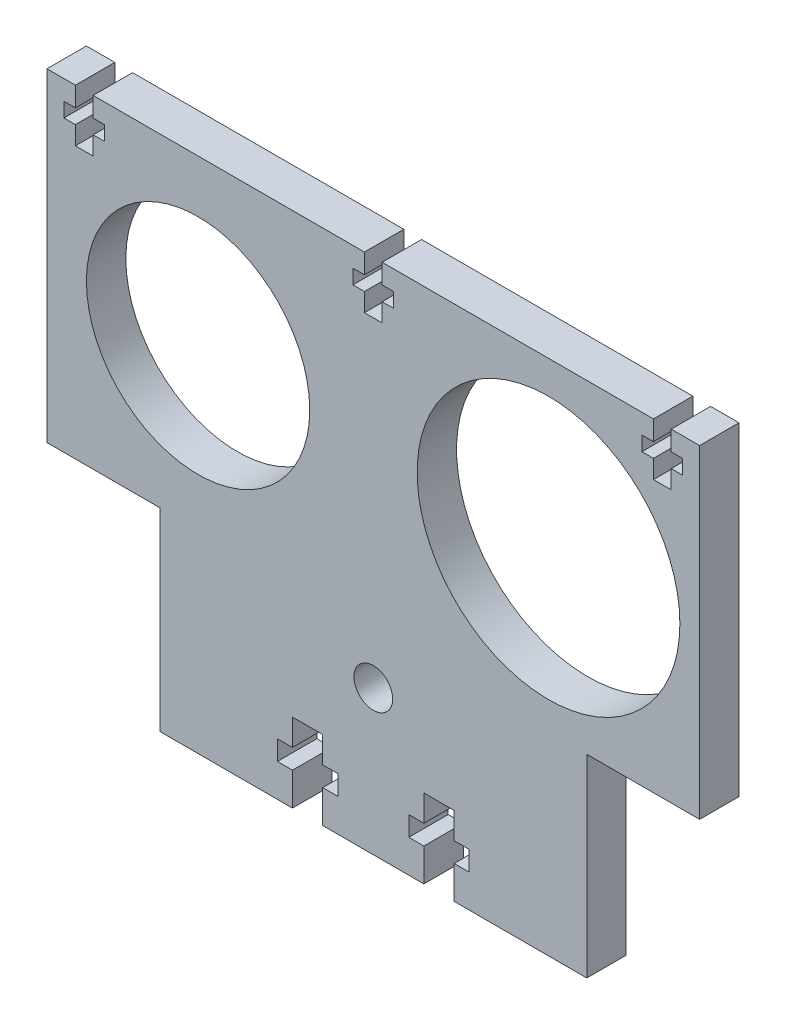
SolidWorks part; units mm, degrees
material "ABS"
ref_plane "Front Plane" through (0, 0, 0) normal (0, 0, 1) x (1, 0, 0)
ref_plane "Top Plane" through (0, 0, 0) normal (0, 1, 0) x (1, 0, 0)
ref_plane "Right Plane" through (0, 0, 0) normal (1, 0, 0) x (0, 0, -1)
sketch "Sketch1" plane through (0, 0, 0) normal (0, 0, 1) x (1, 0, 0)
  line L0 (0, 0) -> (-26.6757, 31.7908) construction
  line L1 (0, 0) -> (0, 56.7908) construction
  line L2 (-32.5, 7.5) -> (-32.5, -22)
  line L3 (-32.5, -22) -> (32.5, -22)
  line L4 (32.5, 7.5) -> (49.6757, 7.5)
  line L5 (0, 0) -> (0, -22) construction
  line L6 (49.6757, 7.5) -> (49.6757, 56.7908)
  line L7 (0, 0) -> (26.6757, 31.7908) construction
  line L10 (-32.5, 7.5) -> (-49.6757, 7.5)
  line L11 (-49.6757, 7.5) -> (-49.6757, 56.7908)
  line L12 (-49.6757, 56.7908) -> (49.6757, 56.7908)
  line L13 (32.5, 7.5) -> (32.5, -22)
  circle A0 centre (0, 0) radius 2.95
  circle A1 centre (-26.6757, 31.7908) radius 17
  circle A2 centre (26.6757, 31.7908) radius 20
  point P16 (0, 56.7908)
  dimension "D1" = 5.9
  dimension "D9" = 34
  dimension "D10" = 40
  dimension "D2" = 41.5
  dimension "D4" = 40
  dimension "D5" = 22
  dimension "D6" = 65
  dimension "D7" = 29.5
  dimension "D8" = 23
  dimension "D3" = 25
  dimension "D11" = 40
extrude "Boss-Extrude1" add sketch "Sketch1" along normal blind 6
sketch "Sketch3" plane through (0, 0, 6) normal (0, 0, 1) x (1, 0, 0)
  line L0 (-32.5, -22) -> (32.5, -22) construction
  line L1 (-12.3, -22) -> (-7.7, -22)
  line L2 (-12.3, -22) -> (-12.3, -17)
  line L3 (-12.3, -10) -> (-7.7, -10)
  line L4 (-7.7, -22) -> (-7.7, -17)
  line L5 (0, 0) -> (0, -22) construction
  line L6 (-7.7, -14) -> (-5.4, -14)
  line L7 (-14.6, -14) -> (-12.3, -14)
  line L8 (-14.6, -14) -> (-14.6, -17)
  line L9 (-14.6, -17) -> (-12.3, -17)
  line L10 (-5.4, -14) -> (-5.4, -17)
  line L11 (-12.3, -14) -> (-12.3, -10)
  line L12 (-7.7, -17) -> (-5.4, -17)
  line L13 (-7.7, -14) -> (-7.7, -10)
  line L14 (7.7, -14) -> (7.7, -10)
  line L15 (7.7, -17) -> (5.4, -17)
  line L16 (12.3, -14) -> (12.3, -10)
  line L17 (5.4, -14) -> (5.4, -17)
  line L18 (14.6, -17) -> (12.3, -17)
  line L19 (14.6, -14) -> (14.6, -17)
  line L20 (14.6, -14) -> (12.3, -14)
  line L21 (7.7, -14) -> (5.4, -14)
  line L22 (7.7, -22) -> (7.7, -17)
  line L23 (12.3, -10) -> (7.7, -10)
  line L24 (12.3, -22) -> (12.3, -17)
  line L25 (12.3, -22) -> (7.7, -22)
  point P6 (-10, -10)
  point P18 (-13.45, -17)
  dimension "D1" = 4.6
  dimension "D2" = 10
  dimension "D3" = 12
  dimension "D4" = 9.2
  dimension "D5" = 3
  dimension "D6" = 5
extrude "Cut-Extrude2" cut sketch "Sketch3" against normal through all
sketch "Sketch4" plane through (0, 0, 6) normal (0, 0, 1) x (1, 0, 0)
  line L0 (42.65, 56.7908) -> (42.65, 53.7908)
  line L1 (49.6757, 56.7908) -> (-49.6757, 56.7908) construction
  line L2 (42.65, 53.7908) -> (40.9, 53.7908)
  line L3 (40.9, 53.7908) -> (40.9, 51.5908)
  line L4 (40.9, 51.5908) -> (42.65, 51.5908)
  line L5 (42.65, 51.5908) -> (42.65, 48.7908)
  line L6 (42.65, 48.7908) -> (45.35, 48.7908)
  line L7 (45.35, 48.7908) -> (45.35, 51.5908)
  line L8 (45.35, 51.5908) -> (47.1, 51.5908)
  line L9 (47.1, 51.5908) -> (47.1, 53.7908)
  line L10 (47.1, 53.7908) -> (45.35, 53.7908)
  line L11 (45.35, 53.7908) -> (45.35, 56.7908)
  line L12 (45.35, 56.7908) -> (42.65, 56.7908)
  line L13 (0, 0) -> (0, 56.7908) construction
  line L14 (-45.35, 56.7908) -> (-42.65, 56.7908)
  line L15 (-45.35, 53.7908) -> (-45.35, 56.7908)
  line L16 (-47.1, 53.7908) -> (-45.35, 53.7908)
  line L17 (-47.1, 51.5908) -> (-47.1, 53.7908)
  line L18 (-45.35, 51.5908) -> (-47.1, 51.5908)
  line L19 (-45.35, 48.7908) -> (-45.35, 51.5908)
  line L20 (-42.65, 48.7908) -> (-45.35, 48.7908)
  line L21 (-42.65, 51.5908) -> (-42.65, 48.7908)
  line L22 (-40.9, 51.5908) -> (-42.65, 51.5908)
  line L23 (-40.9, 53.7908) -> (-40.9, 51.5908)
  line L24 (-42.65, 53.7908) -> (-40.9, 53.7908)
  line L25 (-42.65, 56.7908) -> (-42.65, 53.7908)
  line L26 (-1.35, 56.7908) -> (1.35, 56.7908)
  line L27 (1.35, 56.7908) -> (1.35, 53.7908)
  line L28 (1.35, 53.7908) -> (3.1, 53.7908)
  line L29 (3.1, 53.7908) -> (3.1, 51.5908)
  line L30 (3.1, 51.5908) -> (1.35, 51.5908)
  line L31 (1.35, 51.5908) -> (1.35, 48.7908)
  line L32 (1.35, 48.7908) -> (-1.35, 48.7908)
  line L33 (-1.35, 48.7908) -> (-1.35, 51.5908)
  line L34 (-1.35, 51.5908) -> (-3.1, 51.5908)
  line L35 (-3.1, 51.5908) -> (-3.1, 53.7908)
  line L36 (-3.1, 53.7908) -> (-1.35, 53.7908)
  line L37 (-1.35, 53.7908) -> (-1.35, 56.7908)
  point P18 (44, 48.7908)
  point P39 (0, 0)
  point P44 (6.3485, 42.7357)
  point P45 (4.4469, 41.7444)
  point P46 (0, 48.7908)
  point P47 (9.3855, 51.2793)
  point P48 (0, 0)
  point P49 (0, 0)
  dimension "D1" = 2.7
  dimension "D2" = 2.2
  dimension "D3" = 6.2
  dimension "D4" = 3
  dimension "D5" = 8
  dimension "D6" = 44
extrude "Cut-Extrude3" cut sketch "Sketch4" against normal through all
equation "\"smallPulleyTeeth\"= 30"
equation "\"largePulleyTeeth\"= 30"
equation "\"eighthThick\"= 3.0mm"
equation "\"sixteenthThick\" = 1.7mm"
equation "\"quarterThick\"=6.0mm"
equation "\"OD\" = 145mm"
equation "\"puckAngle\" = 60.5deg"
equation "\"puckDiam\" = 76.5mm"
equation "\"axlePress\" = 5.9mm"
equation "\"D1@Sketch1\"=\"axlePress\""
equation "\"D1@Boss-Extrude1\"=\"quarterThick\""
equation "\"press\" = 0.2mm"
equation "\"wheelClear\" = 0.3mm"
equation "\"10-32clear\" = 4.8mm"
equation "\"D1@Sketch3\"=\"10-32clear\" - \"press\""
equation "\"6-32clear\" = 3.3mm"
equation "\"8-32clear\" = 4.0mm"
equation "\"wheelHeight\" = 22mm"
equation "\"D5@Sketch1\"=\"wheelHeight\""
equation "\"4-40clear\" = 3.0mm"
equation "\"wheelWell\" = 65mm"
equation "\"D6@Sketch1\"=\"wheelWell\""
equation "\"D7@Sketch1\"=\"eighthThick\"*10 - 0.5"
